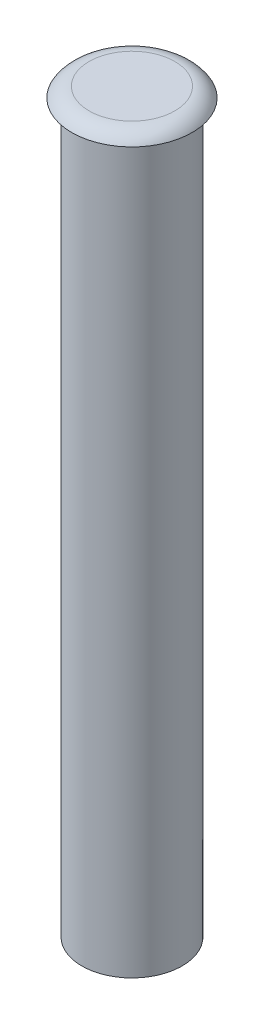
SolidWorks part; units mm, degrees
ref_plane "Front Plane" through (0, 0, 0) normal (0, 0, 1) x (1, 0, 0)
ref_plane "Top Plane" through (0, 0, 0) normal (0, 1, 0) x (1, 0, 0)
ref_plane "Right Plane" through (0, 0, 0) normal (1, 0, 0) x (0, 0, -1)
sketch "Sketch1" plane through (0, 0, 0) normal (0, 1, 0) x (1, 0, 0)
  circle A0 centre (0, 0) radius 2.5
extrude "Boss-Extrude1" add sketch "Sketch1" along normal blind 36.2
sketch "Sketch2" plane through (0, 36.2, 0) normal (0, 1, 0) x (1, 0, 0)
  circle A0 centre (0, 0) radius 3
extrude "Boss-Extrude2" add sketch "Sketch2" along normal blind 0.5
fillet "Fillet2" radius 1 1 edges at (0, 36.7, 3)
